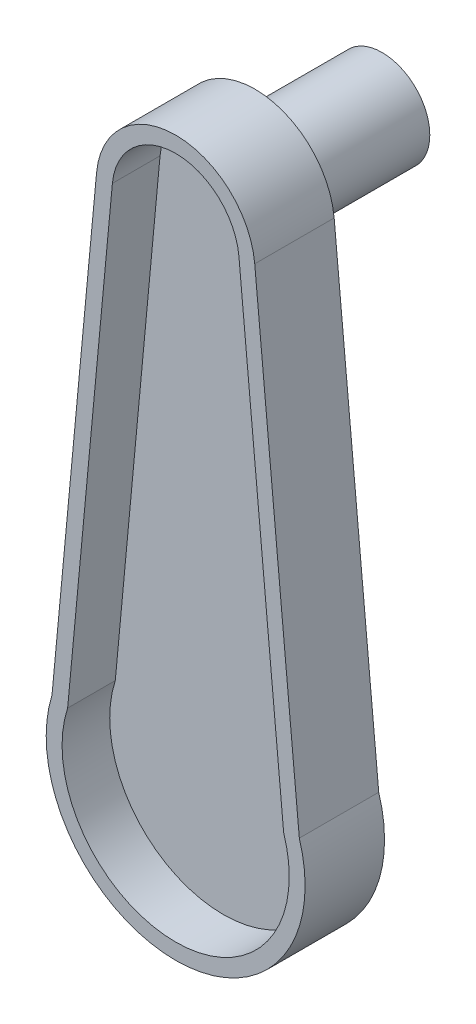
SolidWorks part; units mm, degrees
ref_plane "Front Plane" through (0, 0, 0) normal (0, 0, 1) x (1, 0, 0)
ref_plane "Top Plane" through (0, 0, 0) normal (0, 1, 0) x (1, 0, 0)
ref_plane "Right Plane" through (0, 0, 0) normal (1, 0, 0) x (0, 0, -1)
sketch "Sketch1" plane through (0, 0, 0) normal (0, 0, 1) x (1, 0, 0)
  line L0 (0, 0) -> (0, 15.925) construction
  line L1 (-3.4, 1.1048) -> (0, 1.1048) construction
  line L2 (-3.4, 1.1048) -> (-1.9912, 16.1119)
  line L3 (3.4, 1.1048) -> (1.9912, 16.1119)
  circle A0 centre (0, 0) radius 3.575 construction
  circle A1 centre (0, 15.925) radius 2 construction
  arc A2 (-1.9912, 16.1119) -> (1.9912, 16.1119) centre (0, 15.925) cw
  arc A3 (-3.4, 1.1048) -> (3.4, 1.1048) centre (0, 0) ccw
  point P5 (0, -3.575)
  point P6 (0, 17.925)
  point P7 (-3.4, 1.1048)
  point P14 (1.9907, 16.1172)
  point P15 (0, 0)
  dimension "D1" = 4
  dimension "D2" = 7.15
  dimension "D3" = 21.5
  dimension "D4" = 3.4
extrude "Boss-Extrude1" add sketch "Sketch1" along normal blind 1 contours L2 A2 L3 A3
extrude "Extrude-Thin1" add sketch "Sketch1<3>" along normal blind 2.5 thin thin type one direction wall 0.5
sketch "Sketch1<3>" plane through (0, 0, 0) normal (0, 0, 1) x (1, 0, 0) same geometry as "Sketch1"
sketch "Sketch2" plane through (0, 0, 0) normal (0, 0, -1) x (-1, 0, 0)
  circle A0 centre (0, 15.925) radius 1.5
  dimension "D1" = 3
extrude "Boss-Extrude2" add sketch "Sketch2" along normal blind 4
